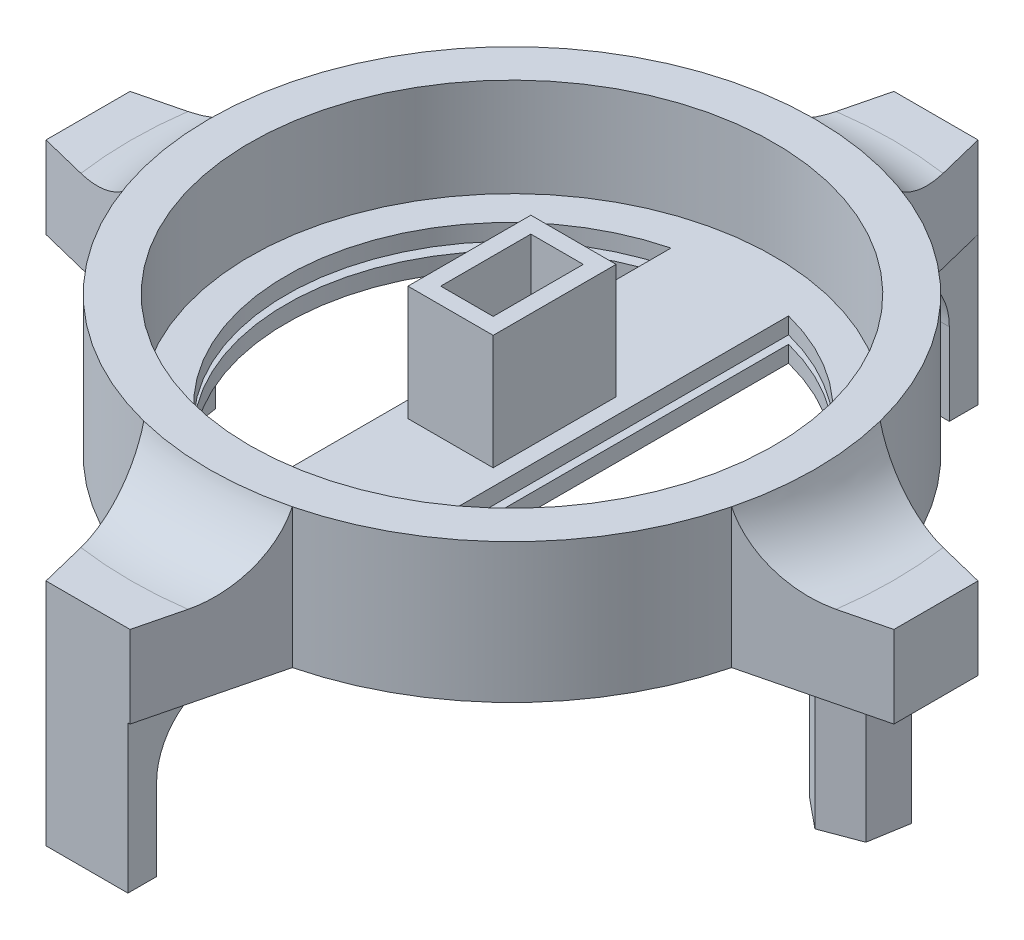
SolidWorks part; units mm, degrees
other "Markup1"
sketch "Sketch14" plane through (-25.8693, -8.5, 20.9211) normal (0, -1, 0) x (1, 0, 0)
other "Markup2"
sketch "Sketch15" plane through (-25.8693, -8.5, 20.9211) normal (0, -1, 0) x (1, 0, 0)
ref_plane "Front Plane" through (0, 0, 0) normal (0, 0, 1) x (1, 0, 0)
ref_plane "Top Plane" through (0, 0, 0) normal (0, 1, 0) x (1, 0, 0)
ref_plane "Right Plane" through (0, 0, 0) normal (1, 0, 0) x (0, 0, -1)
sketch "Sketch4" plane through (0, 0, 0) normal (0, 1, 0) x (1, 0, 0)
  line L0 (0, -46.7905) -> (24.3942, -46.7905) construction
  line L1 (0, -46.7905) -> (0, -24.9936) construction
  circle A0 centre (0, -46.7905) radius 17
  dimension "D1" = 34
extrude "Boss-Extrude3" add sketch "Sketch4" along normal blind 6 separate body
shell "Shell4" thickness 0.5 removed face at (0, 6, 63.7905) outward yes
ref_plane "Plane2" through (0, 0, 0) normal (0, 1, 0) x (1, 0, 0)
sketch "Sketch5" plane through (0, 0, 0) normal (0, 1, 0) x (1, 0, 0)
  line L0 (17, -46.7905) -> (-25.0436, -46.7905) construction
  line L1 (1.6, -44.0405) -> (-1.6, -44.0405)
  line L2 (1.6, -44.0405) -> (1.6, -49.5405)
  line L3 (1.6, -49.5405) -> (-1.6, -49.5405)
  line L4 (-1.6, -44.0405) -> (-1.6, -49.5405)
  line L5 (0, -29.7905) -> (0, -85.3723) construction
  circle A0 centre (0, -46.7905) radius 17 construction
  circle A1 centre (0, -46.7905) radius 17 construction
  dimension "D1" = 5.5
  dimension "D2" = 3.2
  dimension "D3" = 2.75
  dimension "D4" = 1.6
extrude "Boss-Extrude4" add sketch "Sketch5" along normal blind 8
shell "Shell5" thickness 1 removed face at (0, 8, 46.7905) outward yes
sketch "Sketch6" plane through (0, 0, 0) normal (0, 1, 0) x (1, 0, 0)
  line L1 (-2.5652, -72.6598) -> (2.5652, -72.6598)
  line L2 (2.5652, -72.6598) -> (4.5312, -64.727)
  line L3 (-2.5652, -72.6598) -> (-4.5312, -64.727)
  line L4 (-25.8693, -44.2252) -> (-17.9365, -42.2592)
  line L5 (-25.8693, -49.3557) -> (-17.9365, -51.3217)
  line L6 (-25.8693, -44.2252) -> (-25.8693, -49.3557)
  line L7 (2.5652, -20.9211) -> (4.5312, -28.854)
  line L8 (-2.5652, -20.9211) -> (-4.5312, -28.854)
  line L9 (2.5652, -20.9211) -> (-2.5652, -20.9211)
  line L10 (25.8693, -49.3557) -> (17.9365, -51.3217)
  line L11 (25.8693, -44.2252) -> (17.9365, -42.2592)
  line L12 (25.8693, -49.3557) -> (25.8693, -44.2252)
  circle A0 centre (0, -46.7905) radius 18.5 construction
  arc A1 (4.5312, -64.727) -> (-4.5312, -64.727) centre (0, -46.7905) cw
  arc A2 (-17.9365, -51.3217) -> (-17.9365, -42.2592) centre (0, -46.7905) cw
  arc A3 (-4.5312, -28.854) -> (4.5312, -28.854) centre (0, -46.7905) cw
  arc A4 (17.9365, -42.2592) -> (17.9365, -51.3217) centre (0, -46.7905) cw
  point P22 (0, -46.7905)
  dimension "D1" = 4
extrude "Boss-Extrude6" add sketch "Sketch6" against normal up to surface (1.5 mm away) and the other way blind 3.5 up to face at (0, -1.5, 65.2905)
sketch "Sketch7" plane through (0, -1.5, 0) normal (0, -1, 0) x (-1, 0, 0)
  line L0 (0, -20.9211) -> (0, -83.0743) construction
  line L1 (2.5652, -72.6598) -> (-2.4348, -72.6598)
  line L2 (2.5652, -72.6598) -> (2.5652, -70.9098)
  line L3 (2.5652, -70.9098) -> (-2.4348, -70.9098)
  line L4 (-2.4348, -72.6598) -> (-2.4348, -70.9098)
  line L5 (2.5652, -20.9211) -> (-2.5652, -20.9211) construction
  line L6 (25.8693, -46.7905) -> (-32.5376, -46.7905) construction
  line L7 (25.8693, -49.3557) -> (25.8693, -44.2252) construction
  line L12 (-2.5652, -20.9211) -> (-2.5652, -22.6711)
  line L13 (-2.5652, -20.9211) -> (2.4348, -20.9211)
  line L14 (2.4348, -20.9211) -> (2.4348, -22.6711)
  line L15 (-2.5652, -22.6711) -> (2.4348, -22.6711)
  line L20 (25.8693, -44.2252) -> (24.1193, -44.2252) [skipped]
  line L21 (24.1193, -44.2252) -> (24.1193, -49.2252) [skipped]
  line L22 (25.8693, -49.2252) -> (24.1193, -49.2252) [skipped]
  line L23 (25.8693, -44.2252) -> (25.8693, -49.2252) [skipped]
  line L24 (-25.8693, -49.3557) -> (-24.1193, -49.3557) [skipped]
  line L25 (-24.1193, -49.3557) -> (-24.1193, -44.3557) [skipped]
  line L26 (-25.8693, -44.3557) -> (-24.1193, -44.3557) [skipped]
  line L27 (-25.8693, -49.3557) -> (-25.8693, -44.3557) [skipped]
  point P14 (0, -46.7905)
  point P30 (0, -46.7905)
  dimension "D1" = 5
  dimension "D2" = 1.75
  dimension "D3" = 4
extrude "Boss-Extrude7" add sketch "Sketch7" along normal blind 9
fillet "Fillet3" radius 5 4 edges at (0, 3.5, 65.2905) (-18.5, 3.5, 46.7905) (18.5, 3.5, 46.7905) (0, 3.5, 28.2905)
sketch "Sketch11" plane through (0, 1, 0) normal (0, 1, 0) x (1, 0, 0)
  line L0 (-3.5859, -59.9216) -> (-3.5859, -33.5012)
  line L1 (0, -44.0405) -> (0, -17.5543) construction
  line L2 (1.6, -44.0405) -> (-1.6, -44.0405) construction
  line L3 (3.5859, -59.9216) -> (3.5859, -33.5012)
  arc A0 (-3.5859, -59.9216) -> (-3.5859, -33.5012) centre (-0.2324, -46.7114) cw
  arc A1 (3.5859, -59.9216) -> (3.5859, -33.5012) centre (0.2324, -46.7114) ccw
extrude "Cut-Extrude1" cut sketch "Sketch11" against normal blind 5
sketch "Sketch13" plane through (0, -0.5, 0) normal (0, 1, 0) x (1, 0, 0)
  line L1 (-1.566, -49.504) -> (1.6, -49.504)
  line L2 (-1.566, -49.504) -> (-1.566, -44.0405)
  line L3 (-1.566, -44.0405) -> (1.6, -44.0405)
  line L4 (1.6, -49.504) -> (1.6, -44.0405)
extrude "Cut-Extrude2" cut sketch "Sketch13" against normal blind 5
fillet "Fillet4" radius 4 2 edges at (0.0652, -1.5, 22.6711) (-0.0652, -1.5, 70.9098)
sketch "Sketch16" plane through (0, -1.5, 0) normal (0, -1, 0) x (-1, 0, 0)
  line L0 (-0.017, -49.504) -> (-0.017, -17.3421) construction
  line L1 (19.0951, -47.7692) -> (20.962, -49.3051)
  line L2 (20.962, -49.3051) -> (23.2256, -48.4562)
  line L3 (23.2256, -48.4562) -> (23.6223, -46.0715)
  line L4 (23.6223, -46.0715) -> (21.7554, -44.5356)
  line L5 (21.7554, -44.5356) -> (19.4918, -45.3844)
  line L6 (19.4918, -45.3844) -> (19.0951, -47.7692)
  line L7 (1.566, -49.504) -> (-1.6, -49.504) construction
  line L8 (-19.5258, -45.3844) -> (-19.1291, -47.7692)
  line L9 (-21.7893, -44.5356) -> (-19.5258, -45.3844)
  line L10 (-23.6563, -46.0715) -> (-21.7893, -44.5356)
  line L11 (-23.2596, -48.4562) -> (-23.6563, -46.0715)
  line L12 (-20.996, -49.3051) -> (-23.2596, -48.4562)
  line L13 (-19.1291, -47.7692) -> (-20.996, -49.3051)
  circle A0 centre (21.3587, -46.9203) radius 2.0936 construction
extrude "Boss-Extrude8" add sketch "Sketch16" along normal blind 8
